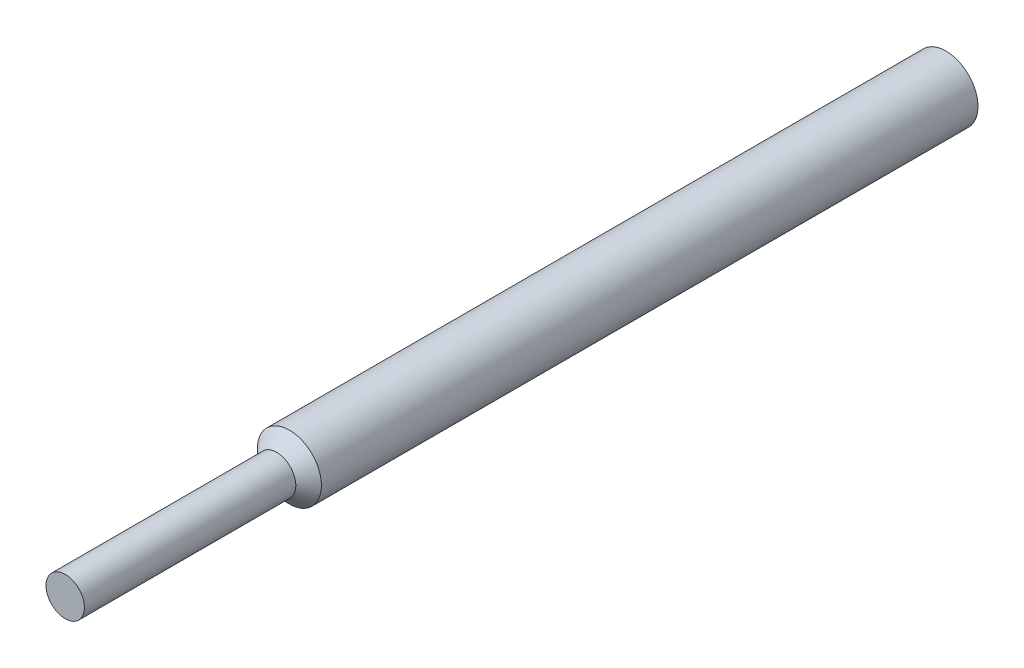
SolidWorks part; units mm, degrees
ref_plane "Front Plane" through (0, 0, 0) normal (0, 0, 1) x (1, 0, 0)
ref_plane "Top Plane" through (0, 0, 0) normal (0, 1, 0) x (1, 0, 0)
ref_plane "Right Plane" through (0, 0, 0) normal (1, 0, 0) x (0, 0, -1)
sketch "Sketch1" plane through (0, 0, 0) normal (1, 0, 0) x (0, 0, -1)
  line L0 (0, 0) -> (0, 6)
  line L1 (0, 6) -> (66, 6)
  line L2 (66, 6) -> (66, 10)
  line L3 (66, 10) -> (275, 10)
  line L4 (275, 10) -> (275, 0)
  line L5 (275, 0) -> (0, 0)
  dimension "D1" = 6
  dimension "D2" = 66
  dimension "D3" = 275
  dimension "D4" = 10
revolve "Revolve1" add sketch "Sketch1" angle 360 about L5
chamfer "Chamfer1" distance 4 angle 45 1 edges at (0, 10, -66)
